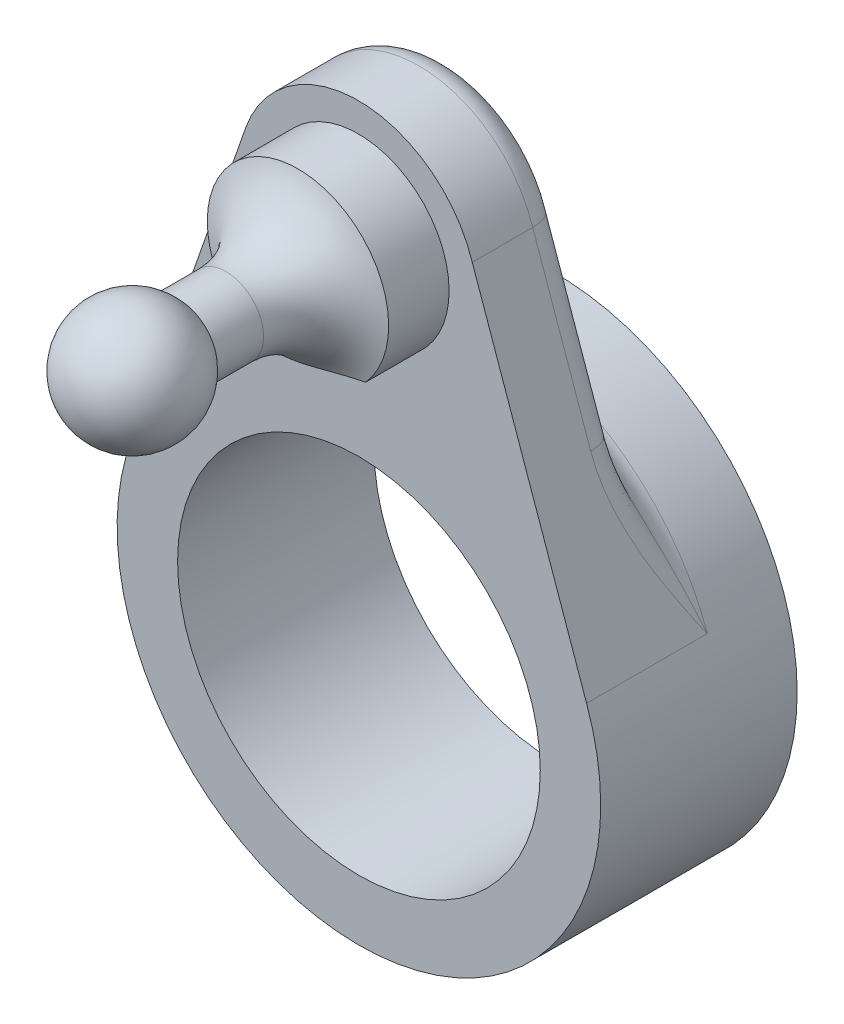
SolidWorks part; units mm, degrees
ref_plane "Płaszczyzna przednia" through (0, 0, 0) normal (0, 0, 1) x (1, 0, 0)
ref_plane "Płaszczyzna górna" through (0, 0, 0) normal (0, 1, 0) x (1, 0, 0)
ref_plane "Płaszczyzna prawa" through (0, 0, 0) normal (1, 0, 0) x (0, 0, -1)
sketch "okrag" plane through (0, 0, 0) normal (0, 0, 1) x (1, 0, 0)
  circle A0 centre (0, 0) radius 8
  circle A1 centre (0, 0) radius 6
  dimension "D1" = 12
  dimension "D2" = 16
extrude "tuleja" add sketch "okrag" along normal blind 6.5
ref_plane "gora-tulei" through (0, 0, 6.5) normal (0, 0, 1) x (1, 0, 0)
sketch "wystep" plane through (0, 0, 6.5) normal (0, 0, 1) x (1, 0, 0)
  line L7 (-3.75, 13.5401) -> (-7.5, 2.7839)
  line L8 (3.75, 13.4413) -> (7.5319, 2.6963)
  circle A0 centre (0, 0) radius 8 construction
  arc A1 (-3.75, 13.5401) -> (3.75, 13.4413) centre (-0.0165, 12.2384) cw
  arc A2 (-7.5, 2.7839) -> (7.5319, 2.6963) centre (0, 0) cw
  dimension "D2" = 3.9539
  dimension "D1" = 12.2384
  dimension "D4" = 3.75
  dimension "D5" = 3.75
  dimension "D6" = 7.5
extrude "wystep-3d" add sketch "wystep" against normal blind 3 contours A1 L8 A2 L7
sketch "Szkic3" plane through (0, 0, 6.5) normal (0, 0, 1) x (1, 0, 0)
  line L0 (-2.2526, 10.2384) -> (2.2196, 10.2384)
  arc A0 (2.2196, 10.2384) -> (-2.2526, 10.2384) centre (-0.0165, 12.2384) ccw
  dimension "D1" = 6
  dimension "D2" = 4.4721
extrude "wypustka" add sketch "Szkic3" along normal blind 2 contours A0 L0
sketch "Szkic4" plane through (0, 0, 6.5) normal (0, 0, 1) x (1, 0, 0)
  circle A0 centre (-0.0165, 12.2384) radius 1.25
  dimension "D1" = 2.5
extrude "pret" add sketch "Szkic4" along normal blind 6
ref_plane "Płaszczyzna3" through (0, 12.2084, 0) normal (0, -1, 0) x (-1, 0, 0)
sketch "Szkic6" plane through (0, 12.2084, 0) normal (0, -1, 0) x (-1, 0, 0)
  line L1 (0, -12) -> (0, -14)
  line L2 (0, -14) -> (0, -16)
  arc A0 (0, -12) -> (0, -16) centre (0, -14) ccw
  dimension "D2" = 14
  dimension "D1" = 2
revolve "Obrót1" add sketch "Szkic6" angle 360 about L1
fillet "Zaokrąglenie1" radius 2.5 1 edges at (1.2335, 12.2384, 8.5)
fillet "Zaokrąglenie2" radius 1 1 edges at (0.0466, 7.9999, 3.5)
fillet "Zaokrąglenie4" radius 1 5 edges at (-4.9721, 10.0347, 3.5) (-7.4552, 2.9123, 2.5879) (7.5193, 2.7323, 2.5243) (4.9636, 9.9934, 3.5) (0.0356, 16.192, 3.5)
ref_plane "Płaszczyzna4" through (0, 0, 2.8) normal (0, 0, 1) x (1, 0, 0)
sketch "Szkic7" plane through (0, 0, 2.8) normal (0, 0, 1) x (1, 0, 0)
  line L2 (0, 0) -> (-6, 8.2464)
  point P1 (6, 8.2464)
  point P3 (0, 0)
  point P4 (0, 0)
  point P6 (0, 0)
  dimension "D1" = 6
  dimension "D2" = 8.2464
ref_plane "Płaszczyzna5" through (-4.7067, 6.4689, 0) normal (-0.5883, 0.8086, 0) x (0.8086, 0.5883, 0)
sketch "Szkic8" plane through (-4.7067, 6.4689, 0) normal (-0.5883, 0.8086, 0) x (0.8086, 0.5883, 0)
  line L0 (0, 0) -> (0, -2.8)
  circle A0 centre (0, -2.8) radius 1.1
  dimension "D2" = 2.2
  dimension "D1" = 2.8
extrude "otwor-kolka" cut sketch "Szkic8" against normal blind 16 and the other way blind 2 contours A0
sketch "Szkic9" plane through (-4.7067, 6.4689, 0) normal (-0.5883, 0.8086, 0) x (0.8086, 0.5883, 0)
  circle A0 centre (0, -2.8) radius 2.25
  dimension "D1" = 4.5
extrude "wybranie" cut sketch "Szkic9" along normal blind 3
ref_plane "Płaszczyzna6" through (0, 0, 3.5) normal (0, 0, -1) x (-1, 0, 0)
sketch "Szkic10" plane through (0, 0, 3.5) normal (0, 0, -1) x (-1, 0, 0)
  text T0 "P" font "Verdana" height 3.5
  dimension "D1" = 1.5
  dimension "D2" = 10.6507
extrude "oznaczenie-strony" add sketch "Szkic10" along normal blind 0.25
